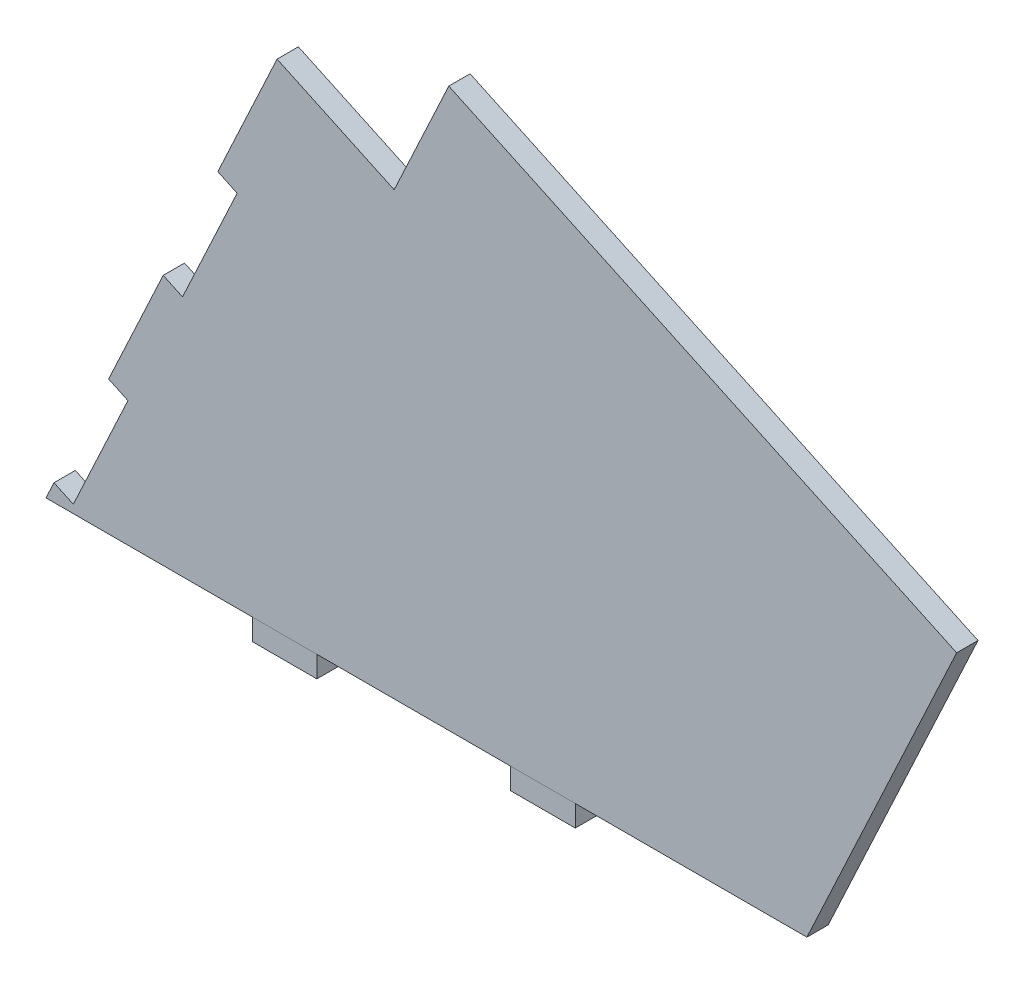
SolidWorks part; units mm, degrees
material "Balsa"
ref_plane "Front Plane" through (0, 0, 0) normal (0, 0, 1) x (1, 0, 0)
ref_plane "Top Plane" through (0, 0, 0) normal (0, 1, 0) x (1, 0, 0)
ref_plane "Right Plane" through (0, 0, 0) normal (1, 0, 0) x (0, 0, -1)
sketch "Sketch1" plane through (0, 0, 396.7) normal (0, 0, 1) x (1, 0, 0)
  line L0 (-321.5462, 12.6346) -> (-203.7639, 12.6346)
  line L2 (-321.5462, 12.6346) -> (-285.7774, 89.341)
  line L3 (-285.7774, 89.341) -> (-267.6513, 80.8887)
  line L4 (-267.6513, 80.8887) -> (-259.1989, 99.0148)
  line L5 (-259.1989, 99.0148) -> (-180.5794, 62.354)
  line L6 (-180.5794, 62.354) -> (-203.7639, 12.6346)
  line L7 (-176.6689, 0) -> (-153.4844, 49.7193) construction
  line L8 (-255.5737, 97.3243) -> (63.4467, -51.4373) construction
  line L10 (-327.4362, 0.0035) -> (-285.7774, 89.341) construction
  line L11 (-285.7774, 89.341) -> (-267.6513, 80.8887) construction
  line L12 (-267.6513, 80.8887) -> (-259.1989, 99.0148) construction
  point P10 (-203.7639, 12.6346)
  point P11 (-321.5462, 12.6346)
extrude "Boss-Extrude1" add sketch "Sketch1" against normal blind 3.3
sketch "Sketch2" plane through (0, 0, 396.7) normal (0, 0, 1) x (1, 0, 0)
  line L0 (-311.8564, 33.4145) -> (-320.3088, 15.2883)
  line L1 (-311.8564, 33.4145) -> (-308.8656, 32.0199)
  line L2 (-320.3088, 15.2883) -> (-317.3179, 13.8937)
  line L3 (-308.8656, 32.0199) -> (-317.3179, 13.8937)
  line L4 (-303.404, 51.5407) -> (-294.9517, 69.6668)
  line L5 (-303.404, 51.5407) -> (-300.4132, 50.146)
  line L6 (-294.9517, 69.6668) -> (-291.9609, 68.2722)
  line L7 (-300.4132, 50.146) -> (-291.9609, 68.2722)
  line L8 (-300.4132, 50.146) -> (-291.9609, 68.2722) construction
  line L9 (-303.404, 51.5407) -> (-294.9517, 69.6668) construction
extrude "Cut-Extrude1" cut sketch "Sketch2" against normal blind 3.3
sketch "Sketch3" plane through (0, 0, 396.7) normal (0, 0, 1) x (1, 0, 0)
  line L0 (-239.6178, 9.3346) -> (-249.6178, 9.3346)
  line L1 (-239.6178, 9.3346) -> (-239.6178, 12.6346)
  line L2 (-249.6178, 9.3346) -> (-249.6178, 12.6346)
  line L3 (-239.6178, 12.6346) -> (-249.6178, 12.6346)
  line L4 (-279.6178, 9.3346) -> (-289.6178, 9.3346)
  line L5 (-279.6178, 9.3346) -> (-279.6178, 12.6346)
  line L6 (-289.6178, 9.3346) -> (-289.6178, 12.6346)
  line L7 (-279.6178, 12.6346) -> (-289.6178, 12.6346)
  line L8 (-321.5462, 12.6346) -> (-203.7639, 12.6346) construction
extrude "Boss-Extrude2" add sketch "Sketch3" against normal blind 3.3 separate body
